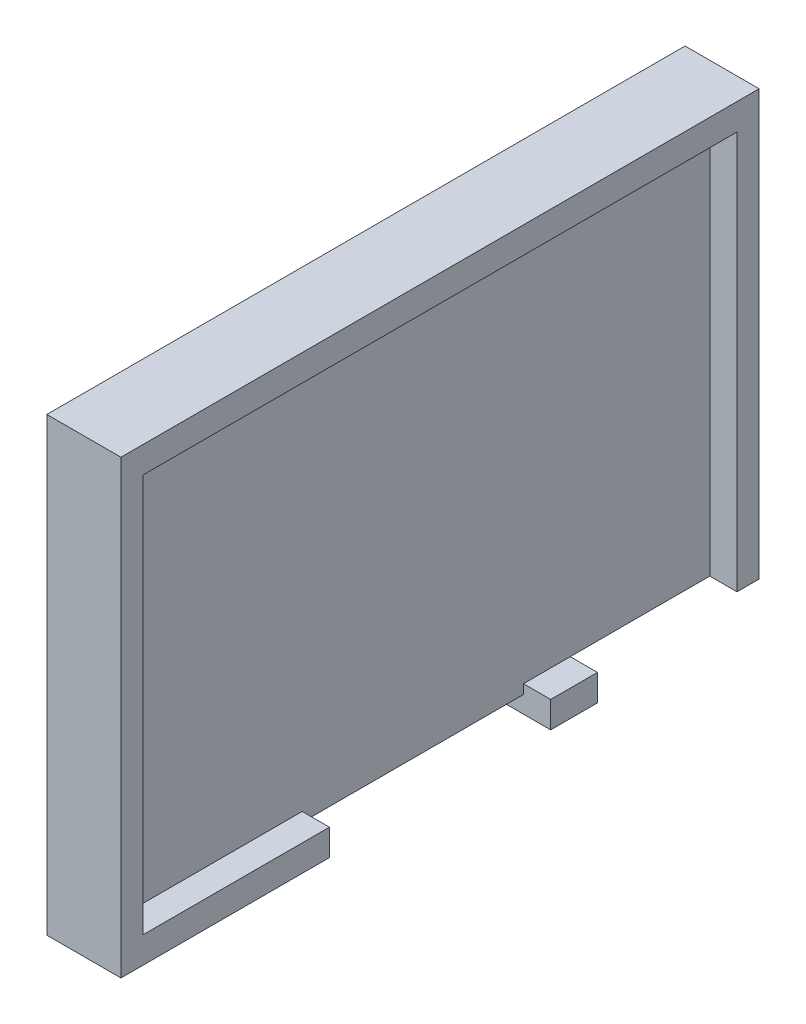
SolidWorks part; units mm, degrees
ref_plane "Front Plane" through (0, 0, 0) normal (1, 0, 0) x (0, 1, 0)
ref_plane "Top Plane" through (0, 0, 0) normal (0, 0, 1) x (0, 1, 0)
ref_plane "Right Plane" through (0, 0, 0) normal (0, 1, 0) x (-1, 0, 0)
sketch "Sketch1" plane through (0, 0, 0) normal (1, 0, 0) x (0, 1, 0)
  line L0 (42.12, 117.43) -> (42.12, 129.18) construction
  line L1 (44.62, 126.68) -> (71.12, 126.68)
  line L2 (44.62, 126.68) -> (44.62, 89.18)
  line L3 (44.62, 89.18) -> (71.12, 89.18)
  line L4 (71.12, 126.68) -> (71.12, 89.18)
  line L5 (42.12, 129.18) -> (89.12, 129.18) construction
  dimension "D1" = 26.5
  dimension "D2" = 37.5
  dimension "D3" = 2.5
  dimension "D4" = 2.5
extrude "Boss-Extrude1" add sketch "Sketch1" along normal blind 4.353 contours L2 L3 L4 L1
sketch "Sketch2" plane through (4.353, 0, 0) normal (1, 0, 0) x (0, 1, 0)
  line L0 (57.87, 126.68) -> (57.87, 89.18)
  line L1 (44.62, 126.68) -> (71.12, 126.68) construction
  line L2 (44.62, 89.18) -> (71.12, 89.18) construction
  line L3 (44.62, 107.93) -> (71.12, 107.93)
  line L4 (44.62, 126.68) -> (44.62, 89.18) construction
  line L5 (71.12, 126.68) -> (71.12, 89.18) construction
  line L7 (69.57, 90.48) -> (46.17, 90.48)
  line L8 (69.57, 90.48) -> (69.57, 125.38)
  line L9 (69.57, 125.38) -> (46.17, 125.38)
  line L10 (46.17, 90.48) -> (46.17, 125.38)
  line L11 (69.57, 90.48) -> (46.17, 125.38) construction
  line L12 (69.57, 125.38) -> (46.17, 90.48) construction
  point P12 (57.87, 107.93)
  dimension "D1" = 23.4
  dimension "D2" = 34.9
extrude "Cut-Extrude1" cut sketch "Sketch2" against normal blind 1.6 contours L7 L10 L9 L8
sketch "Sketch3" plane through (4.353, 0, 0) normal (1, 0, 0) x (0, 1, 0)
  line L0 (44.62, 107.93) -> (46.17, 107.93)
  line L1 (44.62, 126.68) -> (44.62, 89.18) construction
  line L2 (46.17, 90.48) -> (46.17, 125.38) construction
  line L3 (46.17, 125.38) -> (46.17, 126.68)
  line L4 (44.62, 126.68) -> (71.12, 126.68) construction
  line L5 (45.395, 107.93) -> (45.395, 126.68)
  line L7 (46.17, 101.43) -> (44.62, 101.43)
  line L8 (46.17, 101.43) -> (46.17, 114.43)
  line L9 (46.17, 114.43) -> (44.62, 114.43)
  line L10 (44.62, 101.43) -> (44.62, 114.43)
  line L11 (46.17, 101.43) -> (44.62, 114.43) construction
  line L12 (46.17, 114.43) -> (44.62, 101.43) construction
  dimension "D1" = 13
extrude "Cut-Extrude2" cut sketch "Sketch3" against normal blind 1.6 contours L7 L10 L9 L8
sketch "Sketch4" plane through (0, 44.62, 0) normal (0, -1, 0) x (1, 0, 0)
  line L0 (0, 126.68) -> (0, 89.18) construction
  line L1 (2.753, 101.43) -> (0, 101.43)
  line L2 (2.753, 101.43) -> (2.753, 114.43)
  line L3 (2.753, 114.43) -> (0, 114.43)
  line L4 (0, 101.43) -> (0, 114.43)
extrude "Cut-Extrude3" cut sketch "Sketch4" against normal blind 1
sketch "Sketch5" plane through (4.353, 0, 0) normal (1, 0, 0) x (0, 1, 0)
  line L0 (46.17, 90.48) -> (46.17, 101.43) construction
  line L1 (44.62, 89.18) -> (46.17, 89.18)
  line L2 (44.62, 89.18) -> (44.62, 98.68)
  line L3 (44.62, 98.68) -> (46.17, 98.68)
  line L4 (46.17, 89.18) -> (46.17, 98.68)
  dimension "D1" = 9.5
extrude "Cut-Extrude5" cut sketch "Sketch5" against normal blind 1.6 contours L2 L1 L4 L3
sketch "Sketch6" plane through (0, 0, 89.18) normal (0, 0, -1) x (1, 0, 0)
  line L0 (4.353, -46.17) -> (1.953, -46.17)
  line L1 (1.953, -46.17) -> (1.953, -49.12)
  line L2 (1.953, -49.12) -> (0, -49.12)
  line L3 (0, -44.62) -> (0, -71.12) construction
  line L4 (0, -49.12) -> (0, -44.62)
  line L5 (0, -44.62) -> (2.753, -44.62)
  line L6 (2.753, -44.62) -> (2.753, -46.17)
  line M1 (2.753, -46.17) -> (2.753, -44.62)
  line M2 (2.753, -44.62) -> (0, -44.62)
  line M3 (0, -44.62) -> (0, -71.12)
  dimension "D1" = 2.4
  dimension "D2" = 2.95
extrude "Cut-Extrude6" cut sketch "Sketch6" against normal blind 9.5 contours L2 L1 L0 M1 M2 M3 region at (1.1467, 46.6876, 89.18)
